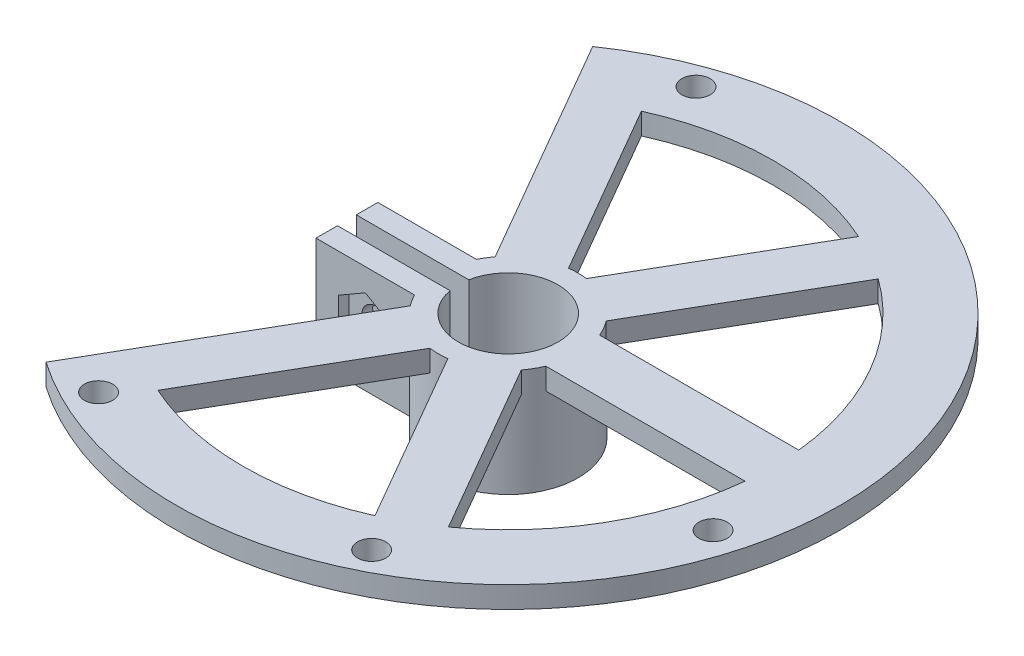
SolidWorks part; units mm, degrees
ref_plane "Front Plane" through (0, 0, 0) normal (0, 0, 1) x (1, 0, 0)
ref_plane "Top Plane" through (0, 0, 0) normal (0, 1, 0) x (1, 0, 0)
ref_plane "Right Plane" through (0, 0, 0) normal (1, 0, 0) x (0, 0, -1)
sketch "Sketch1" plane through (0, 0, 0) normal (0, 1, 0) x (1, 0, 0)
  line L0 (0, 0) -> (21.59, -6.35) construction
  line L1 (0, 0) -> (-7.62, 0) construction
  line L2 (0, 0) -> (0, 21.59) construction
  line L3 (0, 21.59) -> (-7.62, 21.59) construction
  line L4 (-7.62, 0) -> (-7.62, 21.59) construction
  line L5 (0, 0) -> (21.59, 0) construction
  line L6 (0, 0) -> (0, -6.35) construction
  line L7 (0, -6.35) -> (21.59, -6.35) construction
  line L8 (21.59, 0) -> (21.59, -6.35) construction
  line L9 (0, 0) -> (-10.16, 0) construction
  line L10 (0, 0) -> (0, -20.32) construction
  line L11 (0, -20.32) -> (-10.16, -20.32) construction
  line L12 (-10.16, 0) -> (-10.16, -20.32) construction
  line L13 (0, 0) -> (10.16, 0) construction
  line L14 (0, 0) -> (0, -20.32) construction
  line L15 (0, -20.32) -> (10.16, -20.32) construction
  line L16 (10.16, 0) -> (10.16, -20.32) construction
  line L17 (23.6985, -2.54) -> (28.16, -2.54)
  line L18 (-13.208, -20.701) -> (0, 0) construction
  line L19 (0, 0) -> (19.812, 0) construction
  line L20 (0, 0) -> (0, -10.668) construction
  line L21 (0, -10.668) -> (19.812, -10.668) construction
  line L22 (19.812, 0) -> (19.812, -10.668) construction
  line L23 (0, 0) -> (6.223, 0) construction
  line L24 (0, 0) -> (0, -21.844) construction
  line L25 (0, -21.844) -> (6.223, -21.844) construction
  line L26 (6.223, 0) -> (6.223, -21.844) construction
  line L27 (0, 0) -> (12.065, 0) construction
  line L28 (0, 0) -> (0, 19.431) construction
  line L29 (0, 19.431) -> (12.065, 19.431) construction
  line L30 (12.065, 0) -> (12.065, 19.431) construction
  line L31 (0, 0) -> (-13.208, 0) construction
  line L32 (0, 0) -> (0, -26.289) construction
  line L33 (0, -26.289) -> (-13.208, -26.289) construction
  line L34 (-13.208, 0) -> (-13.208, -26.289) construction
  line L35 (0, 0) -> (-7.62, 0) construction
  line L36 (0, 0) -> (0, -26.289) construction
  line L37 (0, -26.289) -> (-7.62, -26.289) construction
  line L38 (-7.62, 0) -> (-7.62, -26.289) construction
  line L39 (0, 0) -> (-13.208, 0) construction
  line L40 (0, 0) -> (0, -20.701) construction
  line L41 (0, -20.701) -> (-13.208, -20.701) construction
  line L42 (-13.208, 0) -> (-13.208, -20.701) construction
  line L44 (-8.62, -26.289) -> (-12.208, -26.289)
  line L45 (-13.208, -25.289) -> (-13.208, -20.9928)
  line L47 (-13.051, -20.455) -> (-11.5519, -18.1054)
  line L48 (-7.62, -25.289) -> (-7.62, -19.6963)
  line L49 (0, 0) -> (29.16, 0) construction
  line L50 (0, 0) -> (0, -6.35) construction
  line L51 (0, -6.35) -> (29.16, -6.35) construction
  line L52 (29.16, 0) -> (29.16, -6.35) construction
  line L53 (0, 0) -> (23.368, 0) construction
  line L54 (0, 0) -> (0, -2.54) construction
  line L55 (0, -2.54) -> (23.368, -2.54) construction
  line L56 (23.368, 0) -> (23.368, -2.54) construction
  line L57 (21.59, -8.35) -> (28.16, -8.35)
  line L58 (29.16, -7.35) -> (29.16, -3.54)
  line L59 (23.1026, -2.737) -> (20.3981, -4.7439)
  circle A0 centre (-7.62, 21.59) radius 1.05
  circle A1 centre (-10.16, -20.32) radius 1.05
  circle A2 centre (10.16, -20.32) radius 1.05
  circle A3 centre (21.59, -6.35) radius 1.05
  circle A4 centre (0, 0) radius 20 construction
  arc A5 (20.3981, -4.7439) -> (21.59, -8.35) centre (21.59, -6.35) ccw
  arc A10 (10.16, -20.32) -> (8.1222, -21.2169) centre (0, 0) cw construction
  arc A11 (8.8372, -23.0848) -> (11.0544, -22.1089) centre (0, 0) ccw
  arc A12 (7.4071, -19.3491) -> (9.2656, -18.5311) centre (0, 0) ccw
  arc A13 (7.4071, -19.3491) -> (8.8372, -23.0848) centre (8.1222, -21.2169) ccw
  arc A14 (11.0544, -22.1089) -> (9.2656, -18.5311) centre (10.16, -20.32) ccw
  arc A15 (-7.62, 21.59) -> (10.2434, 20.4759) centre (0, 0) cw construction
  arc A16 (11.183, 22.354) -> (-8.3189, 23.5703) centre (0, 0) ccw
  arc A17 (9.3039, 18.5979) -> (-6.9211, 19.6097) centre (0, 0) ccw
  arc A18 (9.3039, 18.5979) -> (11.183, 22.354) centre (10.2434, 20.4759) ccw
  arc A19 (-8.3189, 23.5703) -> (-6.9211, 19.6097) centre (-7.62, 21.59) ccw
  arc A21 (-10.2108, -17.7761) -> (-8.2191, -18.7802) centre (0, 0) ccw
  arc A22 (-7.62, -25.289) -> (-8.62, -26.289) centre (-8.62, -25.289) cw
  arc A23 (-12.208, -26.289) -> (-13.208, -25.289) centre (-12.208, -25.289) cw
  arc A24 (-13.208, -20.9928) -> (-13.051, -20.455) centre (-12.208, -20.9928) cw
  arc A25 (-8.2191, -18.7802) -> (-7.62, -19.6963) centre (-8.62, -19.6963) cw
  arc A26 (-11.5519, -18.1054) -> (-10.2108, -17.7761) centre (-10.7089, -18.6432) cw
  arc A27 (23.59, -6.35) -> (21.59, -4.35) centre (21.59, -6.35) ccw construction
  arc A28 (21.59, -8.35) -> (23.59, -6.35) centre (21.59, -6.35) ccw construction
  arc A29 (21.59, -4.35) -> (20.3981, -4.7439) centre (21.59, -6.35) ccw construction
  arc A30 (28.16, -8.35) -> (29.16, -7.35) centre (28.16, -7.35) ccw
  arc A31 (28.16, -2.54) -> (29.16, -3.54) centre (28.16, -3.54) cw
  arc A32 (23.6985, -2.54) -> (23.1026, -2.737) centre (23.6985, -3.54) ccw
  point P34 (9.1521, -20.7934)
  point P44 (1.4251, 22.8509)
  point P57 (-10.7576, -16.8604)
  point P59 (-7.62, -18.4915)
  point P73 (-7.62, -19.0312)
  point P76 (-11.0265, -17.282)
  point P84 (29.16, -2.54)
  dimension "D1" = 7.62
  dimension "D8" = 2.1
  dimension "D9" = 40
  dimension "D13" = 29.16
  dimension "D15" = 2
  dimension "D18" = 2.1
  dimension "D23" = 0.5
  dimension "D24" = 1
  dimension "D27" = 4
  dimension "D28" = 1
  dimension "D2" = 21.59
  dimension "D3" = 10.16
  dimension "D4" = 20.32
  dimension "D5" = 10.16
  dimension "D6" = 6.35
  dimension "D7" = 21.59
  dimension "D10" = 6.223
  dimension "D11" = 19.812
  dimension "D12" = 10.668
  dimension "D14" = 21.844
  dimension "D16" = 12.065
  dimension "D17" = 19.431
  dimension "D19" = 13.208
  dimension "D20" = 26.289
  dimension "D21" = 7.62
  dimension "D22" = 20.701
  dimension "D25" = 2.54
  dimension "D26" = 23.368
extrude "Boss-Extrude1" [suppressed] add sketch "Sketch1" along normal blind 2
sketch "Sketch2" plane through (0, 0, 0) normal (0, 1, 0) x (1, 0, 0)
  line L0 (-3.7, 0) -> (-12, 0) construction
  line L1 (-4.979, 1.5) -> (-12, 1.5) construction
  line L2 (-4.979, -1.5) -> (-12, -1.5) construction
  line L3 (-4.6637, 2.3) -> (-12, 2.3)
  line L4 (-3.6332, -0.7) -> (-12, -0.7)
  line L5 (-3.6332, 0.7) -> (-12, 0.7)
  line L6 (-4.6637, -2.3) -> (-12, -2.3)
  line L7 (-12, 2.3) -> (-12, 0.7)
  line L8 (-12, -0.7) -> (-12, -2.3)
  line L9 (0, 2.3) -> (-2.8983, 2.3) construction
  line L10 (0, 2.3) -> (-12, 2.3) construction
  line L11 (0, 1.5) -> (-3.3823, 1.5) construction
  line L12 (0, 1.5) -> (-12, 1.5) construction
  line L13 (0, 0.7) -> (-3.6332, 0.7) construction
  line L14 (0, 0.7) -> (-12, 0.7) construction
  line L15 (0, 0) -> (-3.7, 0) construction
  line L16 (0, 0) -> (-12, 0) construction
  line L17 (0, -0.7) -> (-3.6332, -0.7) construction
  line L18 (0, -0.7) -> (-12, -0.7) construction
  line L19 (0, -1.5) -> (-3.3823, -1.5) construction
  line L20 (0, -1.5) -> (-12, -1.5) construction
  line L21 (0, -2.3) -> (-2.8983, -2.3) construction
  line L22 (0, -2.3) -> (-12, -2.3) construction
  line L23 (-2.8983, 2.3) -> (-4.6637, 2.3) construction
  line L24 (-3.3823, 1.5) -> (-4.979, 1.5) construction
  line L25 (-2.8983, -2.3) -> (-4.6637, -2.3) construction
  line L26 (-3.3823, -1.5) -> (-4.979, -1.5) construction
  arc A0 (-3.6332, -0.7) -> (-3.6332, 0.7) centre (0, 0) ccw
  arc A1 (-4.6637, -2.3) -> (-4.6637, 2.3) centre (0, 0) ccw
  arc A2 (-4.979, -1.5) -> (-4.6637, -2.3) centre (0, 0) ccw construction
  arc A3 (-5.1527, -0.7) -> (-4.979, -1.5) centre (0, 0) ccw construction
  arc A4 (-4.6637, 2.3) -> (-4.979, 1.5) centre (0, 0) ccw construction
  arc A5 (-5.2, 0) -> (-5.1527, -0.7) centre (0, 0) ccw construction
  arc A6 (-4.979, 1.5) -> (-5.1527, 0.7) centre (0, 0) ccw construction
  arc A7 (-5.1527, 0.7) -> (-5.2, 0) centre (0, 0) ccw construction
  arc A8 (-3.6332, 0.7) -> (-3.7, 0) centre (0, 0) ccw construction
  arc A9 (-3.7, 0) -> (-3.6332, -0.7) centre (0, 0) ccw construction
  dimension "D1" = 7.4
  dimension "D2" = 1.5
  dimension "D3" = 12
  dimension "D4" = 1.5
  dimension "D5" = 1.5
  dimension "D6" = 0.8
  dimension "D7" = 0.8
extrude "Boss-Extrude2" add sketch "Sketch2" along normal blind 8 from offset 10 separate body
sketch "Sketch3" [suppressed] plane through (0, 2, 0) normal (0, 1, 0) x (1, 0, 0)
  line L0 (-7.62, -22.82) -> (-13.208, -22.82)
  line L1 (8.8372, -23.0848) -> (7.4071, -19.3491)
  line L2 (-7.62, -22.82) -> (-7.62, -19.6963) construction
  line L3 (-13.208, -20.9928) -> (-13.208, -22.82) construction
  line L4 (-7.62, -25.289) -> (-7.62, -19.6963)
  line L5 (-11.5519, -18.1054) -> (-13.051, -20.455)
  line L6 (-13.208, -20.9928) -> (-13.208, -25.289)
  line L7 (-12.208, -26.289) -> (-8.62, -26.289)
  line L8 (-7.62, -25.289) -> (-7.62, -22.82) construction
  line L9 (-11.5519, -18.1054) -> (-13.051, -20.455) construction
  line L10 (-13.208, -22.82) -> (-13.208, -25.289)
  line L11 (-12.208, -26.289) -> (-8.62, -26.289)
  line L13 (23.6985, -2.54) -> (23.6985, -8.35)
  line L14 (21.59, -8.35) -> (23.6985, -8.35) construction
  line L15 (-1.2669, 22.8602) -> (0, 0) construction
  line L16 (0, 0) -> (10.3329, 20.4309) construction
  line L17 (29.16, -7.35) -> (29.16, -3.54)
  line L18 (28.16, -2.54) -> (23.6985, -2.54)
  line L19 (23.1026, -2.737) -> (20.3981, -4.7439)
  line L20 (21.59, -8.35) -> (28.16, -8.35)
  line L21 (29.16, -7.35) -> (29.16, -3.54)
  line L22 (28.16, -2.54) -> (23.6985, -2.54)
  line L23 (23.1026, -2.737) -> (20.3981, -4.7439) construction
  line L24 (23.6985, -8.35) -> (28.16, -8.35)
  arc A1 (10.3329, 20.4309) -> (-1.2669, 22.8602) centre (0, 0) ccw construction
  arc A2 (11.2355, 22.2157) -> (-1.3776, 24.8571) centre (0, 0) ccw
  arc A3 (9.4303, 18.6462) -> (-1.1562, 20.8632) centre (0, 0) ccw
  arc A4 (7.4071, -19.3491) -> (8.8372, -23.0848) centre (8.1222, -21.2169) ccw
  arc A5 (8.8372, -23.0848) -> (11.0544, -22.1089) centre (0, 0) ccw
  arc A6 (-8.62, -26.289) -> (-7.62, -25.289) centre (-8.62, -25.289) ccw
  arc A7 (-7.62, -19.6963) -> (-8.2191, -18.7802) centre (-8.62, -19.6963) ccw
  arc A8 (-10.2108, -17.7761) -> (-8.2191, -18.7802) centre (0, 0) ccw
  arc A9 (-10.2108, -17.7761) -> (-11.5519, -18.1054) centre (-10.7089, -18.6432) ccw
  arc A10 (-13.051, -20.455) -> (-13.208, -20.9928) centre (-12.208, -20.9928) ccw
  arc A11 (-13.208, -25.289) -> (-12.208, -26.289) centre (-12.208, -25.289) ccw
  arc A12 (-8.62, -26.289) -> (-7.62, -25.289) centre (-8.62, -25.289) ccw construction
  arc A13 (-7.62, -19.6963) -> (-8.2191, -18.7802) centre (-8.62, -19.6963) ccw construction
  arc A14 (-10.2108, -17.7761) -> (-8.2191, -18.7802) centre (0, 0) ccw construction
  arc A15 (-10.2108, -17.7761) -> (-11.5519, -18.1054) centre (-10.7089, -18.6432) ccw construction
  arc A16 (-13.051, -20.455) -> (-13.208, -20.9928) centre (-12.208, -20.9928) ccw construction
  arc A17 (-13.208, -25.289) -> (-12.208, -26.289) centre (-12.208, -25.289) ccw
  arc A18 (11.0544, -22.1089) -> (9.2656, -18.5311) centre (10.16, -20.32) ccw
  arc A19 (7.4071, -19.3491) -> (9.2656, -18.5311) centre (0, 0) ccw
  arc A20 (7.4071, -19.3491) -> (8.8372, -23.0848) centre (8.1222, -21.2169) ccw construction
  arc A21 (8.8372, -23.0848) -> (11.0544, -22.1089) centre (0, 0) ccw construction
  arc A22 (11.0544, -22.1089) -> (9.2656, -18.5311) centre (10.16, -20.32) ccw construction
  arc A23 (7.4071, -19.3491) -> (9.2656, -18.5311) centre (0, 0) ccw construction
  arc A25 (9.4303, 18.6462) -> (11.2355, 22.2157) centre (10.3329, 20.4309) ccw
  arc A26 (28.16, -8.35) -> (29.16, -7.35) centre (28.16, -7.35) ccw
  arc A27 (29.16, -3.54) -> (28.16, -2.54) centre (28.16, -3.54) ccw
  arc A32 (23.6985, -2.54) -> (23.1026, -2.737) centre (23.6985, -3.54) ccw
  arc A33 (20.3981, -4.7439) -> (21.59, -8.35) centre (21.59, -6.35) ccw
  arc A34 (28.16, -8.35) -> (29.16, -7.35) centre (28.16, -7.35) ccw
  arc A35 (29.16, -3.54) -> (28.16, -2.54) centre (28.16, -3.54) ccw
  arc A36 (23.6985, -2.54) -> (23.1026, -2.737) centre (23.6985, -3.54) ccw construction
  arc A37 (20.3981, -4.7439) -> (21.59, -8.35) centre (21.59, -6.35) ccw construction
  arc A38 (-1.3776, 24.8571) -> (-1.1562, 20.8632) centre (-1.2669, 22.8602) ccw
  arc A39 (9.4303, 18.6462) -> (11.2355, 22.2157) centre (10.3329, 20.4309) ccw construction
  spline S0 degree 3 poles (7.4071, -19.3491) (4.2211, -20.5688) (0.8751, -21.8378) (-5.0583, -22.82) (-7.62, -22.82) knots 0 0 0 0 0.561797 1 1 1 1
  spline S1 degree 3 poles (8.8372, -23.0848) (5.6188, -24.3168) (0.8822, -25.8001) (-5.6018, -26.289) (-8.62, -26.289) knots 0 0 0 0 0.494946 1 1 1 1
  point P0 (-7.62, -22.82)
  point P21 (-10.16, -20.32)
  point P38 (4.6929, 22.4091)
  dimension "D5" = 30
  dimension "D3" = 2.5
  dimension "D4" = 0
  dimension "D1" = 0
  dimension "D2" = 0
extrude "Boss-Extrude3" [suppressed] add sketch "Sketch3" along normal blind 2
sketch "Sketch5" [suppressed] plane through (0, 4, 0) normal (0, 1, 0) x (1, 0, 0)
  line L0 (23.6985, -8.35) -> (28.16, -8.35) construction
  line L1 (29.16, -7.35) -> (29.16, -3.54) construction
  line L2 (28.16, -2.54) -> (23.6985, -2.54) construction
  line L3 (23.6985, -2.54) -> (23.6985, -8.35) construction
  line L4 (8.8372, -23.0848) -> (7.4071, -19.3491) construction
  line L5 (-7.62, -22.82) -> (-13.208, -22.82) construction
  line L6 (-13.208, -22.82) -> (-13.208, -25.289) construction
  line L7 (-12.208, -26.289) -> (-8.62, -26.289) construction
  line L8 (23.6985, -8.35) -> (28.16, -8.35) construction
  line L9 (29.16, -7.35) -> (29.16, -3.54)
  line L10 (28.16, -2.54) -> (23.6985, -2.54) construction
  line L11 (23.6985, -2.54) -> (23.6985, -8.35)
  line L12 (8.8372, -23.0848) -> (7.4071, -19.3491)
  line L13 (-7.62, -22.82) -> (-13.208, -22.82)
  line L14 (-13.208, -22.82) -> (-13.208, -25.289)
  line L15 (-12.208, -26.289) -> (-8.62, -26.289)
  line L16 (2.9834, -20.9706) -> (4.0553, -24.7219) construction
  arc A0 (9.4303, 18.6462) -> (11.2355, 22.2157) centre (10.3329, 20.4309) ccw construction
  arc A1 (11.2355, 22.2157) -> (-1.3776, 24.8571) centre (0, 0) ccw construction
  arc A2 (-1.3776, 24.8571) -> (-1.1562, 20.8632) centre (-1.2669, 22.8602) ccw construction
  arc A3 (9.4303, 18.6462) -> (-1.1562, 20.8632) centre (0, 0) ccw construction
  arc A4 (28.16, -8.35) -> (29.16, -7.35) centre (28.16, -7.35) ccw construction
  arc A5 (29.16, -3.54) -> (28.16, -2.54) centre (28.16, -3.54) ccw construction
  arc A6 (-13.208, -25.289) -> (-12.208, -26.289) centre (-12.208, -25.289) ccw construction
  arc A7 (9.4303, 18.6462) -> (11.2355, 22.2157) centre (10.3329, 20.4309) ccw construction
  arc A8 (11.2355, 22.2157) -> (-1.3776, 24.8571) centre (0, 0) ccw
  arc A9 (-1.3776, 24.8571) -> (-1.1562, 20.8632) centre (-1.2669, 22.8602) ccw
  arc A10 (9.4303, 18.6462) -> (-1.1562, 20.8632) centre (0, 0) ccw
  arc A11 (28.16, -8.35) -> (29.16, -7.35) centre (28.16, -7.35) ccw construction
  arc A12 (29.16, -3.54) -> (29.1551, -3.4413) centre (28.16, -3.54) ccw
  arc A13 (-13.208, -25.289) -> (-12.208, -26.289) centre (-12.208, -25.289) ccw
  arc A14 (29.1551, -3.4413) -> (28.16, -2.54) centre (28.16, -3.54) ccw construction
  spline S0 degree 3 poles (2986.1043, 138.0269) (-226.9594, 31.6479) (87.9124, -84.0037) (-1.1957, 30.2505) (2916.2447, 714.3091) knots -8.140583 -8.140583 -8.140583 -8.140583 0.505054 7.064814 7.064814 7.064814 7.064814 only from (-8.62, -26.289) to (8.8372, -23.0848) construction
  spline S1 degree 3 poles (1953.9415, 439.1191) (-28.0065, -0.4252) (91.668, -33.8744) (-180.4518, -23.8863) (1461.6685, 1330.9522) knots -5.051989 -5.051989 -5.051989 -5.051989 0.561797 7.253557 7.253557 7.253557 7.253557 only from (7.4071, -19.3491) to (-7.62, -22.82) construction
  spline S2 degree 3 poles (-8.62, -26.289) (-5.6018, -26.289) (-0.9023, -25.9346) (2.8793, -25.0579) (4.0553, -24.7219) knots 0 0 0 0 0.505054 0.724787 0.724787 0.724787 0.724787
  spline S3 degree 3 poles (7.4071, -19.3491) (4.2211, -20.5688) (0.8751, -21.8378) (-5.0583, -22.82) (-7.62, -22.82) knots 0 0 0 0 0.561797 1 1 1 1
  spline S4 degree 3 poles (23.6985, -8.35) (23.6985, -10.1666) (23.9904, -13.2388) (16.619, -21.2319) (11.7258, -21.979) (8.8372, -23.0848) knots 0 0 0 0 0.420129 0.520129 1 1 1 1
  spline S5 degree 2 poles (9.4303, 18.6462) (21.7255, 11.4557) (23.6985, -2.54) knots 0 0 0 1 1 1
  spline S6 degree 2 poles (11.2355, 22.2157) (28.2782, 14.7461) (29.16, -3.54) knots 0 0 0 1 1 1
  spline S7 degree 3 poles (29.16, -7.35) (29.16, -13.3885) (27.9427, -21.7873) (5.7926, -30.8014) (4.0553, -24.7219) knots 0 0 0 0 0.521358 1 1 1 1
  spline S8 degree 3 poles (4.0553, -24.7219) (5.5283, -24.301) (7.0476, -23.7698) (8.8372, -23.0848) knots 0.724787 0.724787 0.724787 0.724787 1 1 1 1 construction
  spline M19 degree 3 poles (-8.62, -26.289) (-5.6018, -26.289) (0.8822, -25.8001) (5.6188, -24.3168) (8.8372, -23.0848) knots 0 0 0 0 0.505054 1 1 1 1
  line M20 (8.8372, -23.0848) -> (7.4071, -19.3491)
  spline M21 degree 3 poles (7.4071, -19.3491) (4.2211, -20.5688) (0.8751, -21.8378) (-5.0583, -22.82) (-7.62, -22.82) knots 0 0 0 0 0.561797 1 1 1 1
  line M22 (-7.62, -22.82) -> (-13.208, -22.82)
  line M23 (-13.208, -22.82) -> (-13.208, -25.289)
  arc M24 (-13.208, -25.289) -> (-12.208, -26.289) centre (-12.208, -25.289) ccw
  line M25 (-12.208, -26.289) -> (-8.62, -26.289)
  dimension "D1" = 5
extrude "Boss-Extrude5" [suppressed] add sketch "Sketch5" along normal blind 2 from surface contours M25 M19 M20 M21 M22 M23 M24 | S7 L9 S6 A8 A9 A10 S5 L11 S4 M19
sketch "Sketch6" plane through (0, 0, 2.3) normal (0, 0, 1) x (1, 0, 0)
  line L0 (-12, 18) -> (-4.6637, 10) construction
  line L1 (-4.6637, 18) -> (-12, 10) construction
  circle A0 centre (-8.3318, 14) radius 1.05
  point P11 (-8.3318, 14)
  dimension "D1" = 2.1
extrude "Cut-Extrude1" cut sketch "Sketch6" against normal through all both and the other way through all
sketch "Sketch7" plane through (0, 0, 2.3) normal (0, 0, 1) x (1, 0, 0)
  line L1 (-6.3318, 15.1547) -> (-8.3318, 16.3094)
  line L2 (-8.3318, 16.3094) -> (-10.3318, 15.1547)
  line L3 (-10.3318, 15.1547) -> (-10.3318, 12.8453)
  line L4 (-10.3318, 12.8453) -> (-8.3318, 11.6906)
  line L5 (-8.3318, 11.6906) -> (-6.3318, 12.8453)
  line L6 (-6.3318, 12.8453) -> (-6.3318, 15.1547)
  circle A0 centre (-8.3318, 14) radius 2 construction
  dimension "D1" = 4
extrude "Cut-Extrude2" cut sketch "Sketch7" against normal blind 0.8
sketch "Sketch8" plane through (0, 18, 0) normal (0, -1, 0) x (1, 0, 0)
  line L0 (-9.8592, 17.0767) -> (0, 0) construction
  line L1 (-24.7185, 0) -> (-12.3592, -21.4068) construction
  line L2 (-12.3592, -21.4068) -> (12.3592, -21.4068) construction
  line L3 (12.3592, -21.4068) -> (24.7185, 0) construction
  line L4 (24.7185, 0) -> (12.3592, 21.4068) construction
  line L5 (12.3592, 21.4068) -> (-12.3592, 21.4068) construction
  line L6 (-12.3592, 21.4068) -> (-24.7185, 0) construction
  line L7 (0, 0) -> (9.8592, -17.0767) construction
  line L8 (-9.8592, -17.0767) -> (0, 0) construction
  line L9 (0, 0) -> (9.8592, 17.0767) construction
  line L10 (0, 0) -> (19.7185, 0) construction
  line L11 (-10.5867, -22.3366) -> (-10.0498, -21.4068) construction
  line L12 (0.6679, -5.1569) -> (8.0763, -17.9886)
  line L13 (1.1547, -2) -> (3.4641, -2) construction
  line L14 (1.7321, -1) -> (3.4641, 2) construction
  line L15 (-14.0913, 20.4068) -> (-14.0508, 20.3366) construction
  line L16 (-14.0508, -20.3366) -> (-13.5139, -19.4068) construction
  line L17 (2.3094, 0) -> (3.4641, -2) construction
  line L18 (4.8, 2) -> (19.6168, 2)
  line L19 (0.6679, 5.1569) -> (8.0763, 17.9886)
  line L20 (-10.6272, 22.4068) -> (-10.5867, 22.3366) construction
  line L21 (-13.5139, -19.4068) -> (-11.5404, -15.9886) construction
  line L22 (-11.5404, -15.9886) -> (-4.1321, -3.1569)
  line L23 (-14.0913, -20.4068) -> (-1.7321, 1) construction
  line L24 (-12.3592, -21.4068) -> (-9.8592, -17.0767) construction
  line L25 (-12.3592, -21.4068) -> (0, 0) construction
  line L26 (-10.0498, -21.4068) -> (-8.0763, -17.9886) construction
  line L27 (-8.0763, -17.9886) -> (-0.6679, -5.1569)
  line L28 (-10.6272, -22.4068) -> (1.7321, -1) construction
  line L29 (11.5404, -15.9886) -> (13.5139, -19.4068) construction
  line L30 (13.5139, -19.4068) -> (14.0508, -20.3366) construction
  line L31 (1.7321, 1) -> (14.0913, -20.4068) construction
  line L32 (9.8592, -17.0767) -> (12.3592, -21.4068) construction
  line L33 (0, 0) -> (12.3592, -21.4068) construction
  line L34 (8.0763, -17.9886) -> (10.0498, -21.4068) construction
  line L35 (10.0498, -21.4068) -> (10.5867, -22.3366) construction
  line L36 (-1.7321, -1) -> (10.6272, -22.4068) construction
  line L37 (19.6168, 2) -> (23.5638, 2) construction
  line L38 (24.6374, 2) -> (24.7185, 2) construction
  line L39 (0, 2) -> (24.7185, 2) construction
  line L40 (19.7185, 0) -> (24.7185, 0) construction
  line L41 (0, 0) -> (24.7185, 0) construction
  line L42 (19.6168, -2) -> (23.5638, -2) construction
  line L43 (24.6374, -2) -> (24.7185, -2) construction
  line L44 (0, -2) -> (24.7185, -2) construction
  line L45 (8.0763, 17.9886) -> (10.0498, 21.4068) construction
  line L46 (10.5867, 22.3366) -> (10.6272, 22.4068) construction
  line L47 (-1.7321, 1) -> (10.6272, 22.4068) construction
  line L48 (9.8592, 17.0767) -> (12.3592, 21.4068) construction
  line L49 (0, 0) -> (12.3592, 21.4068) construction
  line L50 (11.5404, 15.9886) -> (13.5139, 19.4068) construction
  line L51 (14.0508, 20.3366) -> (14.0913, 20.4068) construction
  line L52 (1.7321, -1) -> (14.0913, 20.4068) construction
  line L53 (-13.5139, 19.4068) -> (-11.5404, 15.9886) construction
  line L54 (-11.5404, 15.9886) -> (-4.1321, 3.1569)
  line L55 (-14.0913, 20.4068) -> (-1.7321, -1) construction
  line L56 (-12.3592, 21.4068) -> (-9.8592, 17.0767) construction
  line L57 (-12.3592, 21.4068) -> (0, 0) construction
  line L58 (-10.0498, 21.4068) -> (-8.0763, 17.9886) construction
  line L59 (-8.0763, 17.9886) -> (-0.6679, 5.1569)
  line L60 (-10.6272, 22.4068) -> (1.7321, 1) construction
  line L61 (13.5139, 19.4068) -> (14.0508, 20.3366) construction
  line L62 (10.0498, 21.4068) -> (10.5867, 22.3366) construction
  line L63 (23.5638, -2) -> (24.6374, -2) construction
  line L64 (23.5638, 2) -> (24.6374, 2) construction
  line L65 (10.5867, -22.3366) -> (10.6272, -22.4068) construction
  line L66 (14.0508, -20.3366) -> (14.0913, -20.4068) construction
  line L67 (-14.0913, -20.4068) -> (-14.0508, -20.3366) construction
  line L68 (-10.6272, -22.4068) -> (-10.5867, -22.3366) construction
  line L69 (-14.0508, 20.3366) -> (-13.5139, 19.4068) construction
  line L70 (-10.5867, 22.3366) -> (-10.0498, 21.4068) construction
  line L71 (-4.6637, -2.3) -> (-12, -2.3) construction
  line L72 (-1.1547, -2) -> (0, -4) construction
  line L73 (-4.1321, 3.1569) -> (-2.3094, 0) construction
  line L74 (-2.3094, 0) -> (-1.7321, -1) construction
  line L75 (-2.3094, 0) -> (-1.7321, 1) construction
  line L76 (-1.7321, -1) -> (-1.1547, -2) construction
  line L77 (-4.1321, -3.1569) -> (-2.3094, 0) construction
  line L78 (-1.7321, 1) -> (-1.1547, 2) construction
  line L79 (-1.1547, 2) -> (0, 4) construction
  line L80 (0, 4) -> (1.1547, 2) construction
  line L81 (1.1547, 2) -> (1.7321, 1) construction
  line L82 (0, 2) -> (1.1547, 2) construction
  line L83 (1.1547, 2) -> (3.4641, 2) construction
  line L84 (1.7321, 1) -> (2.3094, 0) construction
  line L85 (0, -4) -> (1.1547, -2) construction
  line L86 (1.1547, -2) -> (1.7321, -1) construction
  line L87 (0, -2) -> (1.1547, -2) construction
  line L88 (-0.6679, 5.1569) -> (0, 4) construction
  line L89 (0, 4) -> (0.6679, 5.1569) construction
  line L90 (3.4641, 2) -> (4.1321, 3.1569) construction
  line L91 (4.1321, 3.1569) -> (11.5404, 15.9886)
  line L92 (3.4641, 2) -> (4.8, 2) construction
  line L93 (3.4641, -2) -> (4.8, -2) construction
  line L94 (4.8, -2) -> (19.6168, -2)
  line L95 (3.4641, -2) -> (4.1321, -3.1569) construction
  line L96 (4.1321, -3.1569) -> (11.5404, -15.9886)
  line L97 (-0.6679, -5.1569) -> (0, -4) construction
  line L98 (0, -4) -> (0.6679, -5.1569) construction
  line L99 (-14.0508, 20.3366) -> (-11.5404, 15.9886)
  line L100 (-14.0508, -20.3366) -> (-11.5404, -15.9886)
  circle A0 centre (0, 0) radius 24.7185 construction
  arc A1 (-4.1321, 3.1569) -> (-0.6679, 5.1569) centre (0, 0) cw
  arc A2 (11.0544, 22.1089) -> (8.8372, 23.0848) centre (0, 0) ccw construction
  circle A3 centre (0, 0) radius 24.7185 construction
  arc A4 (11.5404, -15.9886) -> (19.6168, -2) centre (0, 0) ccw
  arc A5 (8.0763, -17.9886) -> (9.8592, -17.0767) centre (0, 0) ccw construction
  circle A6 centre (0, 0) radius 19.7185 construction
  arc A7 (9.8592, -17.0767) -> (11.5404, -15.9886) centre (0, 0) ccw construction
  arc A8 (19.7185, 0) -> (19.6168, 2) centre (0, 0) ccw construction
  arc A9 (19.6168, 2) -> (11.5404, 15.9886) centre (0, 0) ccw
  arc A10 (19.6168, -2) -> (19.7185, 0) centre (0, 0) ccw construction
  arc A11 (9.8592, 17.0767) -> (8.0763, 17.9886) centre (0, 0) ccw construction
  arc A12 (8.0763, 17.9886) -> (-8.0763, 17.9886) centre (0, 0) ccw
  arc A13 (11.5404, 15.9886) -> (9.8592, 17.0767) centre (0, 0) ccw construction
  arc A14 (-11.5404, -15.9886) -> (-9.8592, -17.0767) centre (0, 0) ccw construction
  arc A15 (-8.0763, -17.9886) -> (8.0763, -17.9886) centre (0, 0) ccw
  arc A16 (-9.8592, -17.0767) -> (-8.0763, -17.9886) centre (0, 0) ccw construction
  arc A17 (-9.8592, 17.0767) -> (-11.5404, 15.9886) centre (0, 0) ccw construction
  arc A18 (-11.5404, 15.9886) -> (-11.5404, -15.9886) centre (0, 0) ccw construction
  arc A19 (-8.0763, 17.9886) -> (-9.8592, 17.0767) centre (0, 0) ccw construction
  arc A20 (-4.6637, -2.3) -> (-4.6637, 2.3) centre (0, 0) ccw construction
  arc A21 (-4.6637, 2.3) -> (-4.1321, 3.1569) centre (0, 0) cw construction
  arc A22 (-4.1321, -3.1569) -> (-4.6637, -2.3) centre (0, 0) cw construction
  arc A23 (-0.6679, 5.1569) -> (0.6679, 5.1569) centre (0, 0) cw construction
  arc A24 (0.6679, 5.1569) -> (4.1321, 3.1569) centre (0, 0) cw
  arc A25 (4.1321, 3.1569) -> (4.8, 2) centre (0, 0) cw construction
  arc A26 (4.8, 2) -> (4.8, -2) centre (0, 0) cw
  arc A27 (4.8, -2) -> (4.1321, -3.1569) centre (0, 0) cw construction
  arc A28 (4.1321, -3.1569) -> (0.6679, -5.1569) centre (0, 0) cw
  arc A29 (0.6679, -5.1569) -> (-0.6679, -5.1569) centre (0, 0) cw construction
  arc A30 (-0.6679, -5.1569) -> (-4.1321, -3.1569) centre (0, 0) cw
  arc A31 (-14.0508, 20.3366) -> (-14.0508, -20.3366) centre (0, 0) cw
  dimension "D1" = 5
  dimension "D2" = 2
  dimension "D3" = 2
extrude "Boss-Extrude6" add sketch "Sketch8" along normal blind 1.6
sketch "Sketch9" plane through (0, 18, 0) normal (0, 1, 0) x (1, 0, 0)
  circle A0 centre (-7.62, 21.59) radius 1.05 construction
  circle A1 centre (-7.62, 21.59) radius 1.05
  circle A2 centre (-10.16, -20.32) radius 1.05 construction
  circle A3 centre (10.16, -20.32) radius 1.05 construction
  circle A4 centre (21.59, -6.35) radius 1.05 construction
  circle A5 centre (-10.16, -20.32) radius 1.05
  circle A6 centre (10.16, -20.32) radius 1.05
  circle A7 centre (21.59, -6.35) radius 1.05
extrude "Cut-Extrude3" cut sketch "Sketch9" against normal through all
